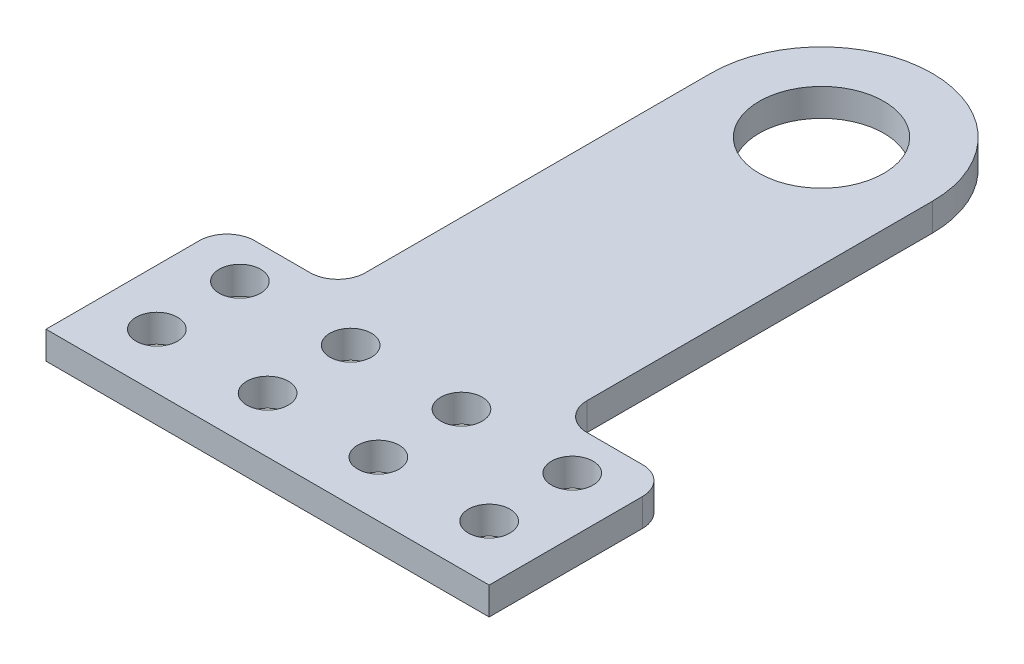
SolidWorks part; units mm, degrees
ref_plane "Front Plane" through (0, 0, 0) normal (0, 0, 1) x (1, 0, 0)
ref_plane "Top Plane" through (0, 0, 0) normal (0, 1, 0) x (1, 0, 0)
ref_plane "Right Plane" through (0, 0, 0) normal (1, 0, 0) x (0, 0, -1)
sketch "Sketch1" plane through (0, 0, 0) normal (0, 1, 0) x (1, 0, 0)
  line L1 (-25.4, -76.2) -> (25.4, -76.2)
  line L2 (-25.4, -76.2) -> (-25.4, 76.2)
  line L3 (-25.4, 76.2) -> (25.4, 76.2)
  line L4 (25.4, -76.2) -> (25.4, 76.2)
  line L5 (-25.4, -76.2) -> (25.4, 76.2) construction
  line L6 (-25.4, 76.2) -> (25.4, -76.2) construction
  line L7 (50.8, -76.2) -> (-50.8, -76.2)
  line L8 (50.8, -76.2) -> (50.8, -34.7066)
  line L9 (50.8, -34.7066) -> (-50.8, -34.7066)
  line L10 (-50.8, -76.2) -> (-50.8, -34.7066)
  line L11 (50.8, -76.2) -> (-50.8, -34.7066) construction
  line L12 (50.8, -34.7066) -> (-50.8, -76.2) construction
  point P0 (0, 0)
  point P6 (0, -55.4533)
  dimension "D1" = 50.8
  dimension "D2" = 152.4
  dimension "D3" = 0
  dimension "D4" = 101.6
  dimension "D5" = 25.4
extrude "Boss-Extrude1" add sketch "Sketch1" along normal blind 6.35 contours L10 L7 L2 L9 | L4 L9 L2 L1 | L9 L4 L3 L2 | L8 L9 L4 L7 region at (0, 0, 55.4533) region at (-38.1, 0, 55.4533) region at (38.1, 0, 55.4533) region at (0, 0, -20.7467)
sketch "Sketch2" plane through (0, 6.35, 0) normal (0, 1, 0) x (1, 0, 0)
  line L0 (25.4, -34.7066) -> (25.4, 76.2) construction
  line L1 (-25.4, 76.2) -> (25.4, 76.2) construction
  circle A0 centre (0, 50.8) radius 14.3002
  point P6 (6.4165, 74.274)
  dimension "D1" = 28.6004
  dimension "D2" = 25.4
  dimension "D3" = 25.4
extrude "Cut-Extrude1" cut sketch "Sketch2" against normal blind 6.35
sketch "Sketch3" plane through (0, 6.35, 0) normal (0, 1, 0) x (1, 0, 0)
  line L0 (50.8, -76.2) -> (-50.8, -76.2) construction
  line L1 (-50.8, -76.2) -> (-50.8, -34.7066) construction
  circle A0 centre (-38.1, -63.5) radius 4.7625
  point P2 (0, 0)
  dimension "D1" = 9.525
  dimension "D2" = 12.7
  dimension "D3" = 12.7
extrude "Cut-Extrude2" cut sketch "Sketch3" against normal blind 6.35
pattern_linear "LPattern1" count 4 spacing 25.4 along (1, 0, 0) count 2 spacing 19.05 along (0, 0, -1) of "Cut-Extrude2"
fillet "Fillet1" radius 6.35 4 edges at (50.8, 3.175, 34.7066) (25.4, 3.175, 34.7066) (-50.8, 3.175, 34.7066) (-25.4, 3.175, 34.7066)
fillet "Fillet2" radius 25.4 2 edges at (25.4, 3.175, -76.2) (-25.4, 3.175, -76.2)
